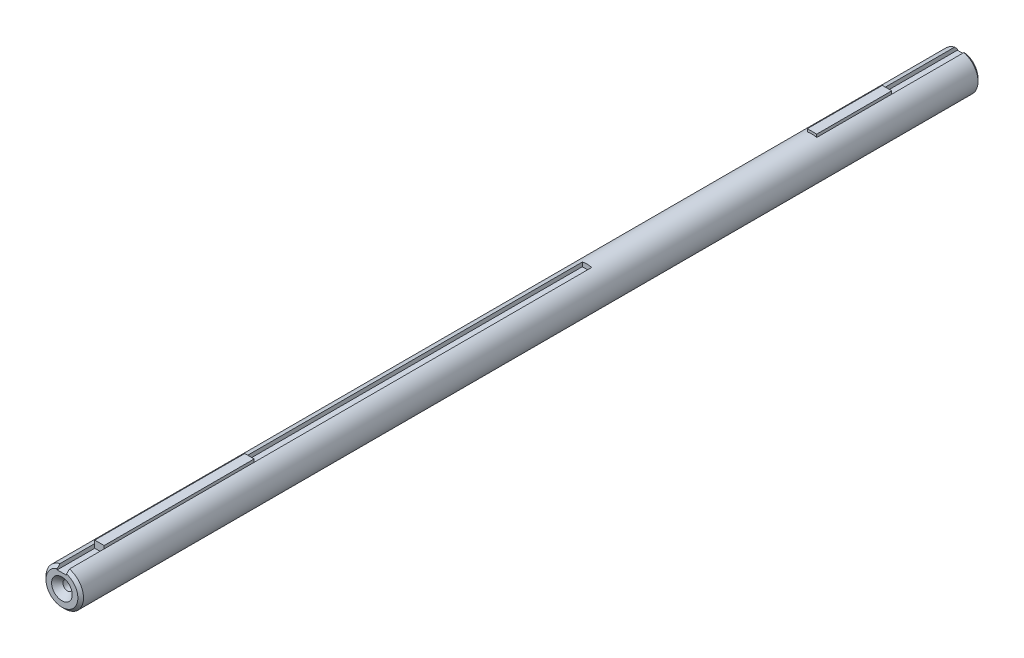
SolidWorks part; units mm, degrees
ref_plane "Front" through (0, 0, 0) normal (0, 0, 1) x (1, 0, 0)
ref_plane "Top" through (0, 0, 0) normal (0, 1, 0) x (1, 0, 0)
ref_plane "Right" through (0, 0, 0) normal (1, 0, 0) x (0, 0, -1)
sketch "Sketch1" plane through (0, 0, 0) normal (0, 0, 1) x (1, 0, 0)
  circle A0 centre (0, 0) radius 12.7
  dimension "dia" = 25.4
extrude "Extrude1" add sketch "Sketch1" along normal mid plane 609.6
sketch "Sketch2" plane through (0, 0, 0) normal (1, 0, 0) x (0, 0, -1)
  point P0 (-304.8, 12.7)
  point P1 (304.8, 12.7)
  point P2 (304.8, -12.7)
chamfer "Chamfer1" distance 1.905 angle 45 2 edges at (12.7, 0, -304.8) (12.7, 0, 304.8)
sketch "Sketch3" plane through (0, 0, 0) normal (0, 0, 1) x (1, 0, 0)
  line L1 (-3.175, 12.7) -> (3.175, 12.7)
  line L2 (-3.175, 12.7) -> (-3.175, 9.525)
  line L3 (-3.175, 9.525) -> (3.175, 9.525)
  line L4 (3.175, 12.7) -> (3.175, 9.525)
  dimension "key wd" = 6.35
  dimension "key dp" = 3.175
extrude "Extrude2" cut sketch "Sketch3" against normal through all and the other way through all
extrude "Extrude3" add sketch "Sketch1<2>" along normal offset from surface 355.6 and the other way offset from surface 101.6 from offset 101.6 up to face at (0, 4.6431, 304.8) other way up to face at (0, 4.6431, -304.8) offset against normal yes
sketch "Sketch1<2>" plane through (0, 0, 0) normal (0, 0, 1) x (1, 0, 0) same geometry as "Sketch1"
ref_plane "Plane1" through (0, 0, 228.6) normal (0, 0, 1) x (1, 0, 0)
ref_plane "Plane2" through (0, 0, -228.6) normal (0, 0, -1) x (-1, 0, 0)
sketch "Sketch5" plane through (0, 0, 228.6) normal (0, 0, 1) x (1, 0, 0)
  line L1 (3.175, 12.7) -> (3.175, 9.525) construction
  line L2 (-3.175, 9.525) -> (3.175, 9.525) construction
  line L3 (-3.175, 12.7) -> (-3.175, 9.525) construction
  line L4 (-3.175, 14.2875) -> (3.175, 14.2875)
  line L5 (3.175, 14.2875) -> (3.175, 9.525)
  line L6 (-3.175, 9.525) -> (3.175, 9.525)
  line L7 (-3.175, 14.2875) -> (-3.175, 9.525)
  dimension "D1" = 4.7625
extrude "Extrude4" add sketch "Sketch5" along normal mid plane 101.6 separate body
sketch "Sketch6" plane through (0, 0, -228.6) normal (0, 0, -1) x (-1, 0, 0)
  line L4 (3.175, 14.2875) -> (-3.175, 14.2875)
  line L5 (-3.175, 14.2875) -> (-3.175, 9.525)
  line L6 (-3.175, 9.525) -> (3.175, 9.525)
  line L7 (3.175, 9.525) -> (3.175, 14.2875)
  line L8 (3.175, 14.2875) -> (-3.175, 14.2875)
  line L9 (-3.175, 14.2875) -> (-3.175, 9.525)
  line L10 (-3.175, 9.525) -> (3.175, 9.525)
  line L11 (3.175, 9.525) -> (3.175, 14.2875)
  dimension "D1" = 0
extrude "Extrude5" add sketch "Sketch6" along normal mid plane 50.8 separate body
sketch "Sketch7" plane through (0, 0, 304.8) normal (0, 0, 1) x (1, 0, 0)
  circle A0 centre (0, 0) radius 3.175
  dimension "D1" = 6.35
extrude "Cut-Extrude1" cut sketch "Sketch7" against normal blind 12.7
sketch "Sketch8" plane through (0, 0, -304.8) normal (0, 0, -1) x (-1, 0, 0)
  circle A0 centre (0, 0) radius 3.175
  dimension "D1" = 6.35
extrude "Cut-Extrude2" cut sketch "Sketch8" against normal blind 12.7
chamfer "Chamfer2" distance 3.81 angle 45 2 edges at (3.175, 0, 304.8) (-3.175, 0, -304.8)
equation "\"D1@Chamfer1\" = \"dia@Sketch1\" * .075"
equation "\"D1@Sketch5\" = \"key dp@Sketch3\" * 1.5"
